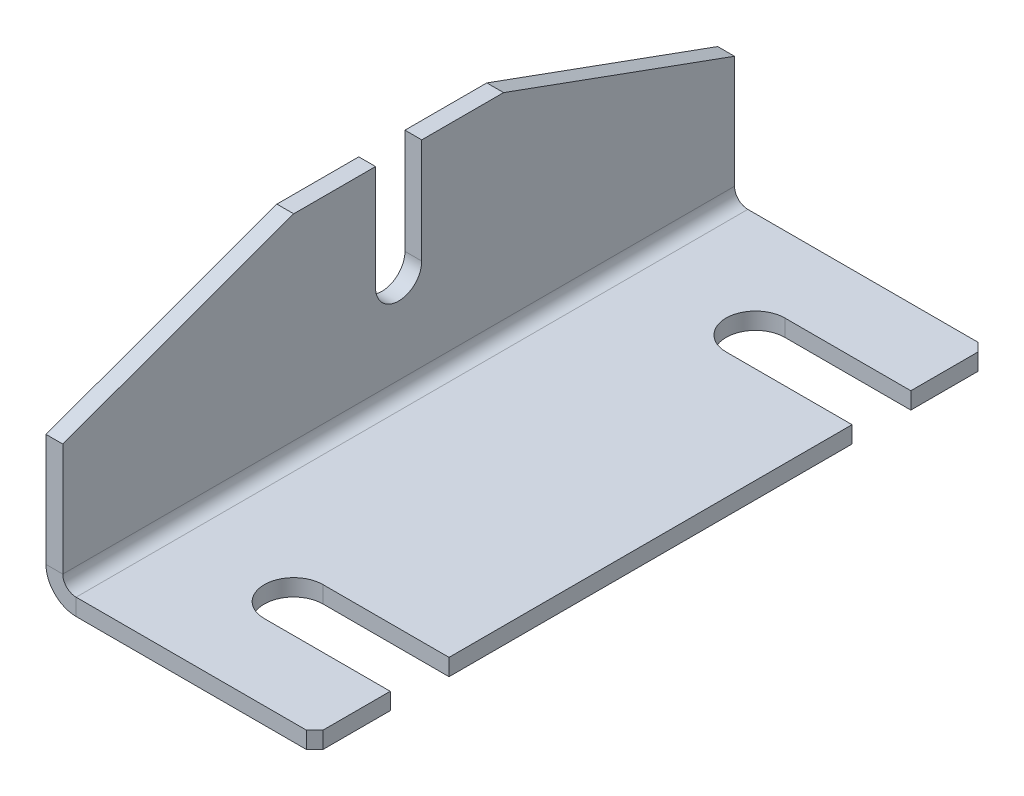
SolidWorks part; units mm, degrees
note: The reader was unsure of these and kept them because the rebuilt part matched: bend radius of "BaseBend1".
ref_plane "Front Plane" through (0, 0, 0) normal (0, 0, 1) x (1, 0, 0)
ref_plane "Top Plane" through (0, 0, 0) normal (0, 1, 0) x (1, 0, 0)
ref_plane "Right Plane" through (0, 0, 0) normal (1, 0, 0) x (0, 0, -1)
sketch "Sketch1" plane through (0, 0, 0) normal (0, 0, 1) x (1, 0, 0)
  line L0 (0, 0) -> (0, 50)
  line L1 (0, 0) -> (60, 0)
  dimension "D1" = 60
  dimension "D2" = 50
base flange "Base-Flange1" sketch "Sketch1" end condition mid plane depth 160 reverse direction no thickness 4 reverse thickness direction no bend radius 3.175
bend "BaseBend1" bend radius 3.175 bend angle 90 parameters "D5"=1
sketch "Sketch6" plane through (0, 0, 0) normal (1, 0, 0) x (0, 0, -1)
  line L0 (0, 0) -> (0, 50) construction
  line L1 (5.5, 25) -> (5.5, 50)
  line L2 (-80, 50) -> (80, 50) construction
  line L3 (-5.5, 25) -> (-5.5, 50)
  line L4 (-5.5, 50) -> (5.5, 50)
  arc A0 (-5.5, 25) -> (5.5, 25) centre (0, 25) ccw
  dimension "D1" = 5.5
  dimension "D2" = 25
extrude "Cut-Extrude1" cut sketch "Sketch6" against normal up to next normal cut yes
sketch "Sketch8" plane through (0, 0, 0) normal (1, 0, 0) x (0, 0, -1)
  line L0 (-80, 30) -> (-25, 50)
  line L1 (-80, 50) -> (-80, 3.175) construction
  line L2 (-80, 50) -> (-5.5, 50) construction
  line L3 (25, 50) -> (80, 30)
  line L4 (5.5, 50) -> (80, 50) construction
  line L5 (80, 50) -> (80, 3.175) construction
  line L6 (-80, 30) -> (-80, 50)
  line L7 (-80, 50) -> (-25, 50)
  line L8 (25, 50) -> (80, 50)
  line L9 (80, 50) -> (80, 30)
  dimension "D1" = 55
  dimension "D2" = 55
  dimension "D3" = 20
  dimension "D4" = 20
extrude "Cut-Extrude2" cut sketch "Sketch8" against normal up to next normal cut yes
sketch "Sketch9" plane through (0, 0, 0) normal (0, 1, 0) x (1, 0, 0)
  line L0 (30, 62) -> (60, 62)
  line L1 (60, -80) -> (60, 80) construction
  line L2 (30, 48) -> (60, 48)
  line L3 (30, -48) -> (60, -48)
  line L4 (30, -62) -> (60, -62)
  line L5 (3.175, 80) -> (60, 80) construction
  line L6 (3.175, -80) -> (60, -80) construction
  line L7 (60, 62) -> (60, 48)
  line L8 (60, -48) -> (60, -62)
  arc A0 (30, 62) -> (30, 48) centre (30, 55) ccw
  arc A1 (30, -48) -> (30, -62) centre (30, -55) ccw
  dimension "D5" = 7
  dimension "D6" = 7
  dimension "D1" = 30
  dimension "D2" = 30
  dimension "D3" = 25
  dimension "D4" = 25
extrude "Cut-Extrude3" cut sketch "Sketch9" against normal up to next normal cut yes
chamfer "Chamfer1" distance 2 angle 45 2 edges at (60, -2, -80) (60, -2, 80)
sketch "Bend-Lines1" [suppressed] plane through (0, 0, 0) normal (0, 1, 0) x (1, 0, 0)
sketch "Bounding-Box1" [suppressed] plane through (0, 0, 0) normal (0, 1, 0) x (1, 0, 0)
sheet metal parameters "Sheet-Metal1" thickness 4 parameters "D1"=3.175
flat pattern "Flat-Pattern1" [suppressed]
sketch "Bend-Lines2" plane through (0, 0, 0) normal (0, 1, 0) x (1, 0, 0)
  line L0 (-0.8894, -80) -> (-0.8894, 80) construction
  line L1 (-0.8894, -80) -> (-0.8894, 80) construction
sketch3d "Bounding-Box2" [suppressed]
  line L0 (-51.7789, 160, 0) -> (-51.7789, 0, 0) construction
  line L1 (60, 160, 0) -> (60, 0, 0) construction
  line L2 (-51.7789, 160, 0) -> (60, 160, 0) construction
  line L3 (-51.7789, 0, 0) -> (60, 0, 0) construction
bend of the flat pattern "Flatten-<BaseBend1>1"
sheet metal parameters "Sheet-Metal2" thickness 4 parameters "D1"=3.175
flat pattern "Flat-Pattern1"
sketch "Bend-Lines2" plane through (0, 0, 0) normal (0, 1, 0) x (1, 0, 0)
  line L0 (-0.8894, -80) -> (-0.8894, 80) construction
  line L1 (-0.8894, -80) -> (-0.8894, 80) construction
sketch3d "Bounding-Box2" [suppressed]
  line L0 (-51.7789, 160, 0) -> (-51.7789, 0, 0) construction
  line L1 (60, 160, 0) -> (60, 0, 0) construction
  line L2 (-51.7789, 160, 0) -> (60, 160, 0) construction
  line L3 (-51.7789, 0, 0) -> (60, 0, 0) construction
bend of the flat pattern "Flatten-<BaseBend1>1"
sheet metal parameters "Sheet-Metal3" thickness 4 parameters "D1"=3.175
flat pattern "Flat-Pattern1"
sketch "Bend-Lines2" plane through (0, 0, 0) normal (0, 1, 0) x (1, 0, 0)
  line L0 (-0.8894, -80) -> (-0.8894, 80) construction
  line L1 (-0.8894, -80) -> (-0.8894, 80) construction
sketch3d "Bounding-Box2" [suppressed]
  line L0 (-51.7789, 160, 0) -> (-51.7789, 0, 0) construction
  line L1 (60, 160, 0) -> (60, 0, 0) construction
  line L2 (-51.7789, 160, 0) -> (60, 160, 0) construction
  line L3 (-51.7789, 0, 0) -> (60, 0, 0) construction
bend of the flat pattern "Flatten-<BaseBend1>1"
sheet metal parameters "Sheet-Metal4" thickness 4 parameters "D1"=3.175
flat pattern "Flat-Pattern1"
sketch "Bend-Lines2" plane through (0, 0, 0) normal (0, 1, 0) x (1, 0, 0)
  line L0 (-0.8894, -80) -> (-0.8894, 80) construction
  line L1 (-0.8894, -80) -> (-0.8894, 80) construction
sketch3d "Bounding-Box2" [suppressed]
  line L0 (-51.7789, 160, 0) -> (-51.7789, 0, 0) construction
  line L1 (60, 160, 0) -> (60, 0, 0) construction
  line L2 (-51.7789, 160, 0) -> (60, 160, 0) construction
  line L3 (-51.7789, 0, 0) -> (60, 0, 0) construction
bend of the flat pattern "Flatten-<BaseBend1>1"
